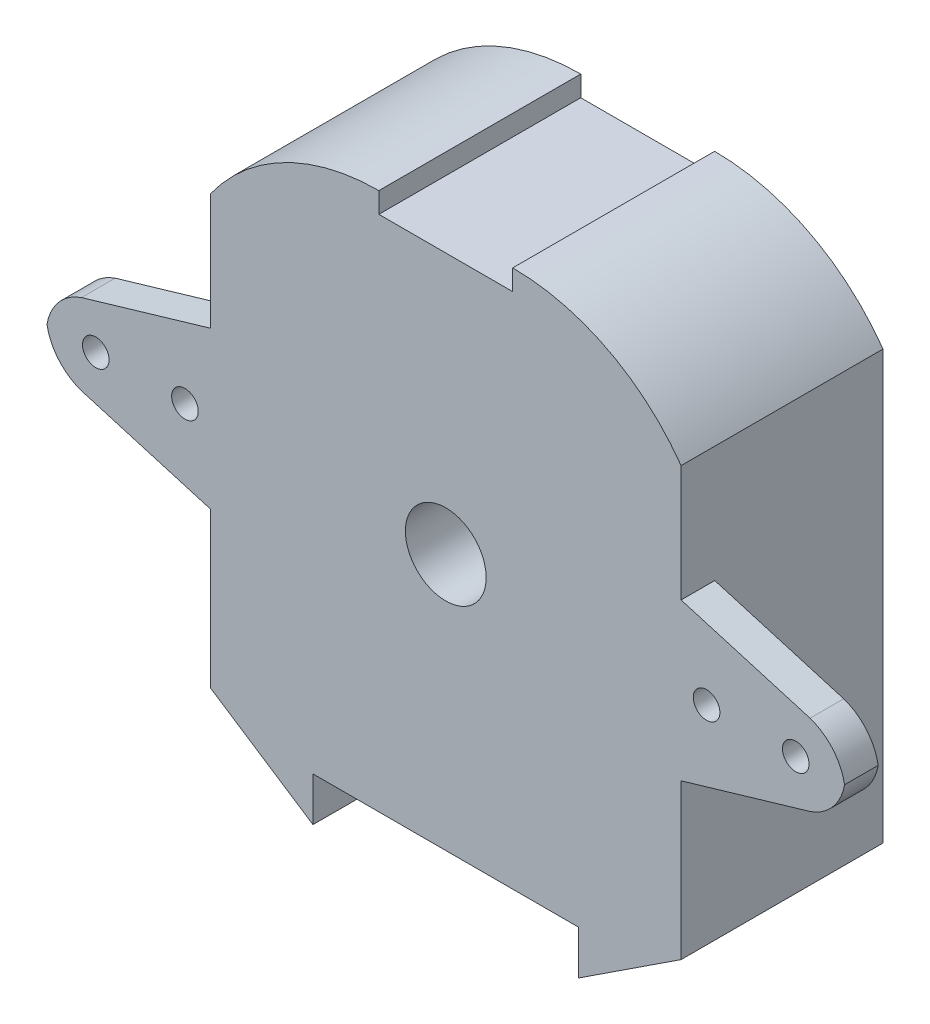
SolidWorks part; units mm, degrees
material "PLA"
ref_plane "Front Plane" through (0, 0, 0) normal (0, 0, 1) x (1, 0, 0)
ref_plane "Top Plane" through (0, 0, 0) normal (0, 1, 0) x (1, 0, 0)
ref_plane "Right Plane" through (0, 0, 0) normal (1, 0, 0) x (0, 0, -1)
sketch "Sketch1" plane through (0, 0, 0) normal (0, 0, 1) x (1, 0, 0)
  line L0 (0, 70.9446) -> (0, 19.6997) construction
  line L2 (-17.7635, 14.683) -> (-17.7635, -17.609)
  line L3 (-17.7635, -17.609) -> (-10.0241, -22.6796)
  line L4 (-10.0241, -22.6796) -> (-10.0241, -19.3595)
  line L5 (-10.0241, -19.3595) -> (10.0241, -19.3595)
  line L6 (-5.0511, 21.2507) -> (-5.0511, 19.6997)
  line L7 (-5.0511, 19.6997) -> (5.0511, 19.6997)
  line L8 (10.0241, -22.6796) -> (10.0241, -19.3595)
  line L9 (17.7635, -17.609) -> (10.0241, -22.6796)
  line L10 (17.7635, 14.683) -> (17.7635, -17.609)
  line L11 (5.0511, 21.2507) -> (5.0511, 19.6997)
  line L13 (0, 19.6997) -> (0, -83.3132) construction
  arc A0 (-5.0511, 21.2507) -> (-17.7635, 14.683) centre (-5.0511, 5.6637) ccw
  arc A1 (5.0511, 21.2507) -> (17.7635, 14.683) centre (5.0511, 5.6637) cw
  point P17 (0, -19.3595)
  point P21 (0, 19.6997)
  point P24 (0, 0)
extrude "Boss-Extrude2" add sketch "Sketch1" along normal blind 15.24
sketch "Sketch5" plane through (0, 0, 15.24) normal (0, 0, 1) x (1, 0, 0)
  circle A0 centre (0, 0) radius 3.048
  dimension "D1" = 6.096
extrude "Cut-Extrude2" cut sketch "Sketch5" against normal blind 15.24
sketch "Sketch6" plane through (0, 0, 15.24) normal (0, 0, 1) x (1, 0, 0)
  line L2 (-27.4971, 3.0373) -> (-17.7635, 5.9001)
  line L3 (-17.7635, 14.683) -> (-17.7635, -17.609) construction
  line L4 (-17.7635, 5.9001) -> (-17.7635, -5.921)
  line L5 (-27.4971, -3.0582) -> (-17.7635, -5.921)
  line L6 (0, 24.5613) -> (0, -29.2199) construction
  line L7 (27.4971, 3.0373) -> (17.7635, 5.9001)
  line L8 (27.4971, -3.0582) -> (17.7635, -5.921)
  line L9 (17.7635, 5.9001) -> (17.7635, -5.921)
  arc A0 (-27.4971, 3.0373) -> (-30.1001, -0.0104) centre (-26.2297, -0.6805) ccw
  arc A1 (-27.4971, -3.0582) -> (-30.1001, -0.0104) centre (-26.2297, 0.6596) cw
  arc A2 (27.4971, 3.0373) -> (30.1001, -0.0104) centre (26.2297, -0.6805) cw
  arc A3 (27.4971, -3.0582) -> (30.1001, -0.0104) centre (26.2297, 0.6596) ccw
  point P3 (-19.5103, 9.4005)
extrude "Boss-Extrude3" add sketch "Sketch6" against normal blind 2.54
sketch "Sketch7" plane through (0, 0, 0) normal (0, 0, -1) x (-1, 0, 0)
  line L0 (-34.7295, 0) -> (42.0609, 0) construction
  line L1 (0, 25.6042) -> (0, -30.1557) construction
  circle A0 centre (-19.685, 0) radius 1.0033
  circle A1 centre (-26.416, 0) radius 1.0033
  circle A2 centre (19.685, 0) radius 1.0033
  circle A3 centre (26.416, 0) radius 1.0033
  dimension "D1" = 2.0066
  dimension "D2" = 2.0066
  dimension "D3" = 39.37
  dimension "D4" = 52.832
extrude "Cut-Extrude5" cut sketch "Sketch7" along normal through all both and the other way through all
